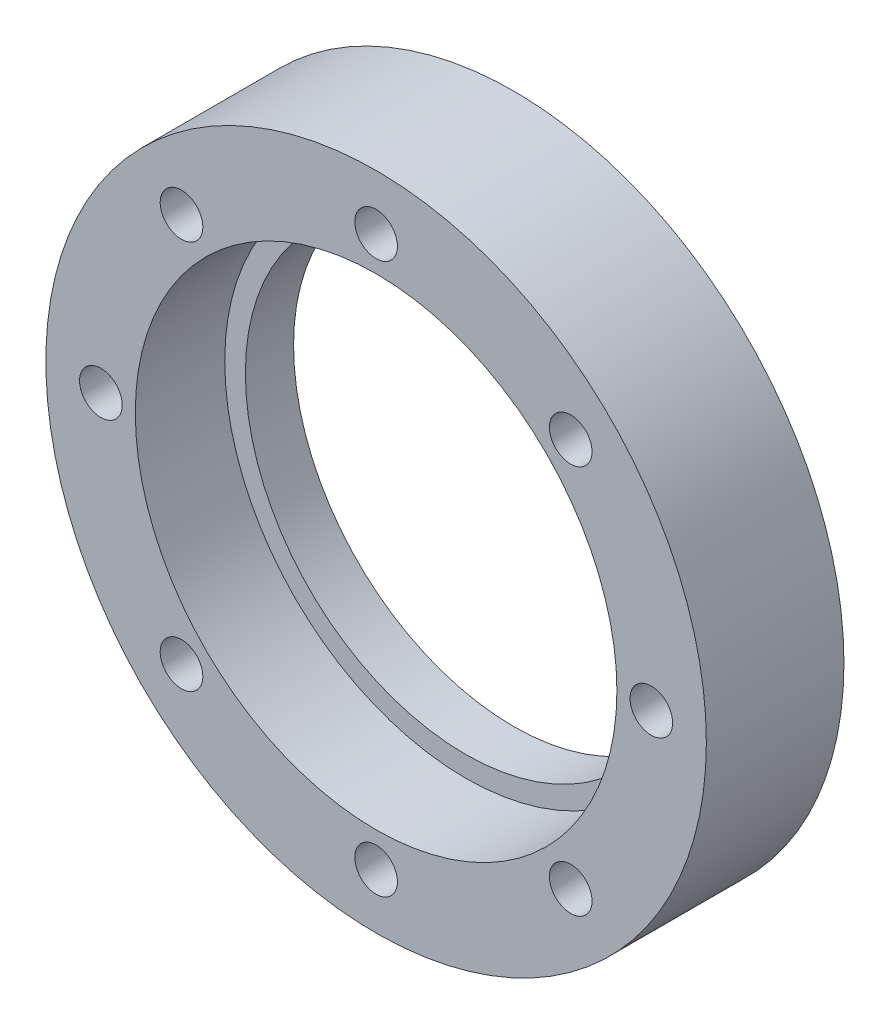
SolidWorks part; units mm, degrees
ref_plane "Front Plane" through (0, 0, 0) normal (0, 0, 1) x (1, 0, 0)
ref_plane "Top Plane" through (0, 0, 0) normal (0, 1, 0) x (1, 0, 0)
ref_plane "Right Plane" through (0, 0, 0) normal (1, 0, 0) x (0, 0, -1)
ref_axis "Axis1" through (0, 0, 5.5) along (0, 0, -1)
sketch "Sketch6" plane through (0, 0, 0) normal (0, 0, 1) x (1, 0, 0)
  line L0 (0, 0) -> (0, 20) construction
  circle A0 centre (0, 0) radius 24
  circle A1 centre (0, 20) radius 1.55
  circle A2 centre (14.1421, 14.1421) radius 1.55
  circle A3 centre (20, 0) radius 1.55
  circle A4 centre (14.1421, -14.1421) radius 1.55
  circle A5 centre (0, -20) radius 1.55
  circle A6 centre (-14.1421, -14.1421) radius 1.55
  circle A7 centre (-20, 0) radius 1.55
  circle A8 centre (-14.1421, 14.1421) radius 1.55
  circle A9 centre (0, 0) radius 16
  point P21 (0, 0)
  dimension "D1" = 8
extrude "Boss-Extrude1" add sketch "Sketch6" along normal blind 10
sketch "Sketch8" plane through (0, 0, 0) normal (0, 0, -1) x (-1, 0, 0)
  line L0 (0, 20) -> (0, 0) construction
  circle A0 centre (0, 20) radius 3.5
  circle A1 centre (14.1421, 14.1421) radius 3.5
  circle A2 centre (20, 0) radius 3.5
  circle A3 centre (14.1421, -14.1421) radius 3.5
  circle A4 centre (0, -20) radius 3.5
  circle A5 centre (-14.1421, -14.1421) radius 3.5
  circle A6 centre (-20, 0) radius 3.5
  circle A7 centre (-14.1421, 14.1421) radius 3.5
  point P20 (0, 0)
  dimension "D1" = 8
extrude "Cut-Extrude6" cut sketch "Sketch8" against normal blind 3
sketch "Sketch9" plane through (0, 0, 10) normal (0, 0, 1) x (1, 0, 0)
  circle A0 centre (0, 0) radius 17.5
extrude "Cut-Extrude7" cut sketch "Sketch9" against normal blind 6.5
